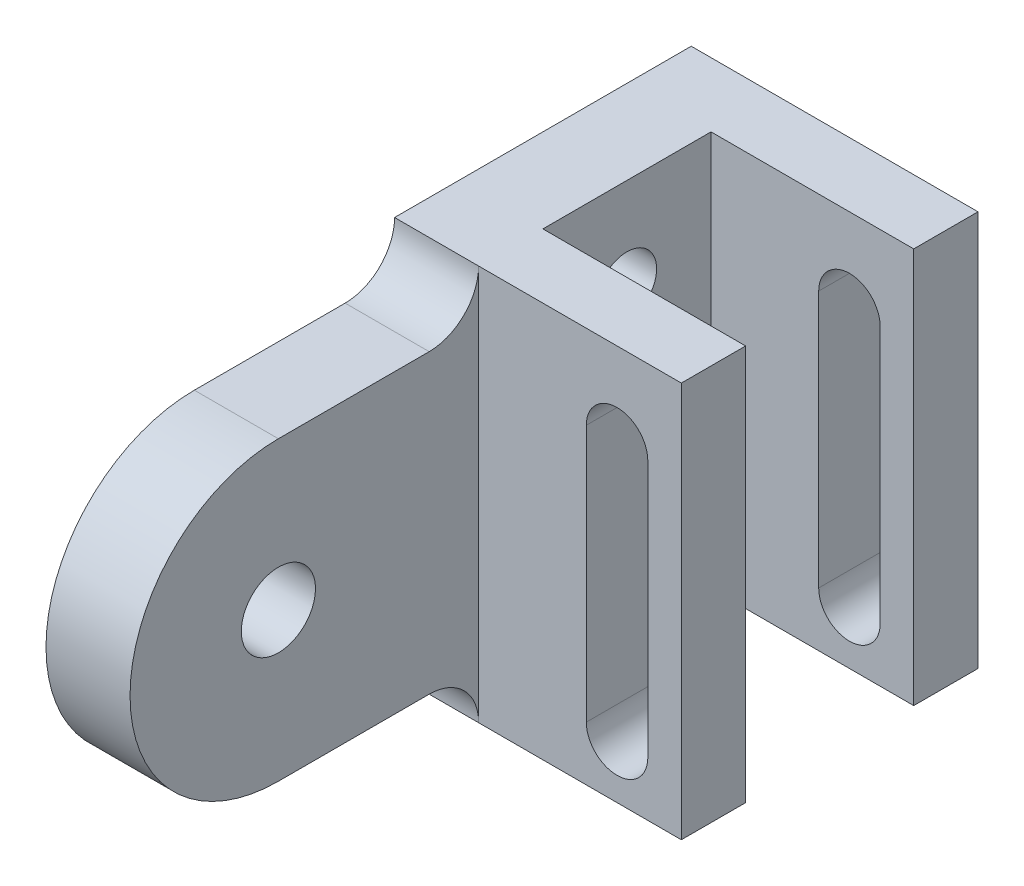
SolidWorks part; units mm, degrees
ref_plane "Front Plane" through (0, 0, 0) normal (0, 0, 1) x (1, 0, 0)
ref_plane "Top Plane" through (0, 0, 0) normal (0, 1, 0) x (1, 0, 0)
ref_plane "Right Plane" through (0, 0, 0) normal (1, 0, 0) x (0, 0, -1)
sketch "Sketch1" plane through (0, 0, 0) normal (0, 1, 0) x (1, 0, 0)
  line L0 (0, 0) -> (58, 0)
  line L1 (58, 0) -> (58, 13)
  line L2 (58, 13) -> (17, 13)
  line L3 (17, 13) -> (17, 47)
  line L4 (17, 47) -> (58, 47)
  line L5 (58, 47) -> (58, 60)
  line L6 (58, 60) -> (0, 60)
  line L7 (0, 60) -> (0, 0)
  point P3 (0, 30)
  point P10 (0, 0)
  point P11 (0, 0)
  point P12 (59.8829, 10.8739)
  dimension "D1" = 17
  dimension "D2" = 58
  dimension "D3" = 13
  dimension "D4" = 34
  dimension "D5" = 13
extrude "Boss-Extrude1" add sketch "Sketch1" along normal blind 80
sketch "Sketch2" plane through (0, 0, 0) normal (0, 0, 1) x (1, 0, 0)
  line L5 (45, 11) -> (45, 63) construction
  line L6 (38.7816, 11) -> (38.7816, 63)
  line L7 (51.2184, 11) -> (51.2184, 63)
  line L8 (58, 80) -> (58, 0) construction
  line L9 (0, 0) -> (58, 0) construction
  arc A0 (38.7816, 11) -> (51.2184, 11) centre (45, 11) ccw
  arc A1 (51.2184, 63) -> (38.7816, 63) centre (45, 63) ccw
  point P6 (45, 37)
  dimension "D1" = 52
  dimension "D4" = 6.2184
  dimension "D2" = 13
  dimension "D3" = 11
extrude "Cut-Extrude1" cut sketch "Sketch2" against normal blind 80
sketch "Sketch4" plane through (17, 0, 0) normal (1, 0, 0) x (0, 0, -1)
  line L0 (13, 0) -> (47, 0) construction
  line L3 (0, 80) -> (0, 0) construction
  circle A0 centre (30, 18.5) radius 6
  circle A1 centre (30, 61.5) radius 6
  point P0 (14.8841, 12.2068)
  dimension "D3" = 12
  dimension "D1" = 18.5
  dimension "D2" = 30
  dimension "D4" = 43
extrude "Cut-Extrude4" cut sketch "Sketch4" against normal blind 80 contours A0 | A1 region at (17, 18.5, -30)
sketch "Sketch8" plane through (0, 0, 0) normal (-1, 0, 0) x (0, 0, 1)
  line L0 (-60, 0) -> (0, 0) construction
  line L1 (0, 80) -> (0, 0) construction
  line L2 (-60, 80) -> (-60, 0) construction
  line L3 (40.5, 70) -> (0, 70)
  line L4 (40.5, 10) -> (0, 10)
  line L5 (0, 10) -> (0, 70)
  line L6 (0, 80) -> (0, 70)
  arc A0 (40.5, 10) -> (40.5, 70) centre (40.5, 40) ccw
  dimension "D2" = 60
  dimension "D1" = 100.5
  dimension "D3" = 40
extrude "Boss-Extrude2" add sketch "Sketch8" against normal blind 17 contours L5 L4 A0 L3
sketch "Sketch9" plane through (0, 0, 0) normal (-1, 0, 0) x (0, 0, 1)
  circle A0 centre (40.5, 40) radius 7.5
  dimension "D1" = 15
extrude "Cut-Extrude5" cut sketch "Sketch9" against normal blind 17
fillet "Fillet2" radius 10 1 edges at (8.5, 70, 0)
fillet "Fillet3" radius 10 1 edges at (8.5, 10, 0)
equation "\"13.00mm`\"=13"
